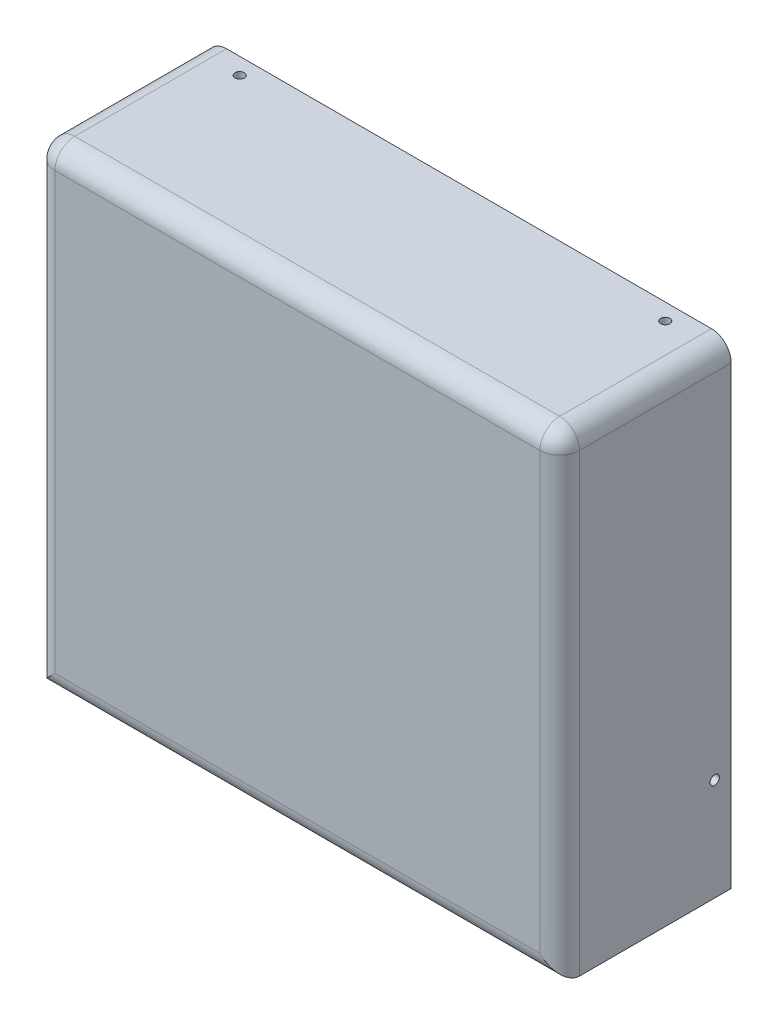
SolidWorks part; units mm, degrees
ref_plane "Front Plane" through (0, 0, 0) normal (0, 0, 1) x (1, 0, 0)
ref_plane "Top Plane" through (0, 0, 0) normal (0, 1, 0) x (1, 0, 0)
ref_plane "Right Plane" through (0, 0, 0) normal (1, 0, 0) x (0, 0, -1)
sketch "Sketch1" plane through (0, 0, 0) normal (0, 0, 1) x (1, 0, 0)
  line L1 (0, 0) -> (196.85, 0)
  line L2 (0, 0) -> (0, -177.8)
  line L3 (0, -177.8) -> (196.85, -177.8)
  line L4 (196.85, 0) -> (196.85, -177.8)
  dimension "D1" = 177.8
  dimension "D2" = 196.85
extrude "Boss-Extrude1" add sketch "Sketch1" along normal blind 63.5
fillet "Fillet1" radius 5.08 6 edges at (98.425, 0, 63.5) (196.85, -88.9, 63.5) (98.425, -177.8, 63.5) (0, -88.9, 63.5) (0, 0, 31.75) (196.85, 0, 31.75)
shell "Shell1" thickness 2.54 removed face at (98.425, -60.6093, 0) outward yes
sketch "Sketch2" plane through (0, -180.34, 0) normal (0, -1, 0) x (1, 0, 0)
  line L0 (0, 0) -> (0, 11.7475)
  line L1 (5.08, 16.8275) -> (191.77, 16.8275)
  line L2 (196.85, 11.7475) -> (196.85, 0)
  line L3 (-2.54, 0) -> (199.39, 0) construction
  line L4 (196.85, 0) -> (0, 0)
  line L5 (5.08, 66.04) -> (191.77, 66.04) construction
  arc A0 (191.77, 16.8275) -> (196.85, 11.7475) centre (191.77, 11.7475) cw
  arc A1 (5.08, 16.8275) -> (0, 11.7475) centre (5.08, 11.7475) ccw
  dimension "D2" = 5.08
  dimension "D1" = 49.2125
  dimension "D3" = 196.85
extrude "Cut-Extrude1" cut sketch "Sketch2" against normal up to surface (2.54 mm away) up to face at (98.425, -177.8, 29.21)
hole_wizard "9/64 (0.14063) Diameter Hole1" positions "Sketch3" profile "Sketch4" hole size "9/64" standard "ANSI Inch"
sketch "Sketch3" plane through (0, 2.54, 0) normal (0, 1, 0) x (1, 0, 0)
  line L0 (5.08, 0) -> (5.08, -58.42) construction
  line L1 (191.77, -58.42) -> (191.77, 0) construction
  line L2 (191.77, 0) -> (5.08, 0) construction
  point P0 (16.51, -6.35)
  point P2 (180.34, -6.35)
  dimension "D1" = 11.43
  dimension "D2" = 11.43
  dimension "D3" = 6.35
sketch "Sketch4" plane through (16.51, 2.54, 6.35) normal (1, 0, 0) x (0, 0, 1)
  line L0 (0, 0) -> (0, 3.6131)
  line L1 (0, 3.6131) -> (1.786, 2.54)
  line L2 (1.786, 2.54) -> (1.786, 0)
  line L5 (1.786, 0) -> (0, 0)
  line L10 (0, 3.6131) -> (-1.786, 2.54) construction
  line L11 (0, -6.35) -> (0, 107.95) construction
  dimension "Hole Dia." = 3.572
  dimension "Hole Depth" = 2.54
  dimension "Drill Angle" = 118
hole_wizard "9/64 (0.14063) Diameter Hole2" positions "Sketch5" profile "Sketch6" hole size "9/64" standard "ANSI Inch" end condition through all
sketch "Sketch5" plane through (-2.54, 0, 0) normal (-1, 0, 0) x (0, 0, 1)
  line L0 (0, -5.08) -> (0, -180.34) construction
  line L2 (58.42, -5.08) -> (0, -5.08) construction
  point P0 (6.35, -140.97)
  dimension "D1" = 6.35
  dimension "D2" = 135.89
sketch "Sketch6" plane through (-2.54, -140.97, 6.35) normal (0, 1, 0) x (0, 0, 1)
  line L0 (0, 0) -> (0, 201.93)
  line L1 (0, 201.93) -> (1.786, 201.93)
  line L2 (1.786, 201.93) -> (1.786, 0)
  line L5 (1.786, 0) -> (0, 0)
  line L11 (0, -6.35) -> (0, 107.95) construction
  dimension "Thru Hole Dia." = 3.572
  dimension "Thru Hole Depth" = 201.93
